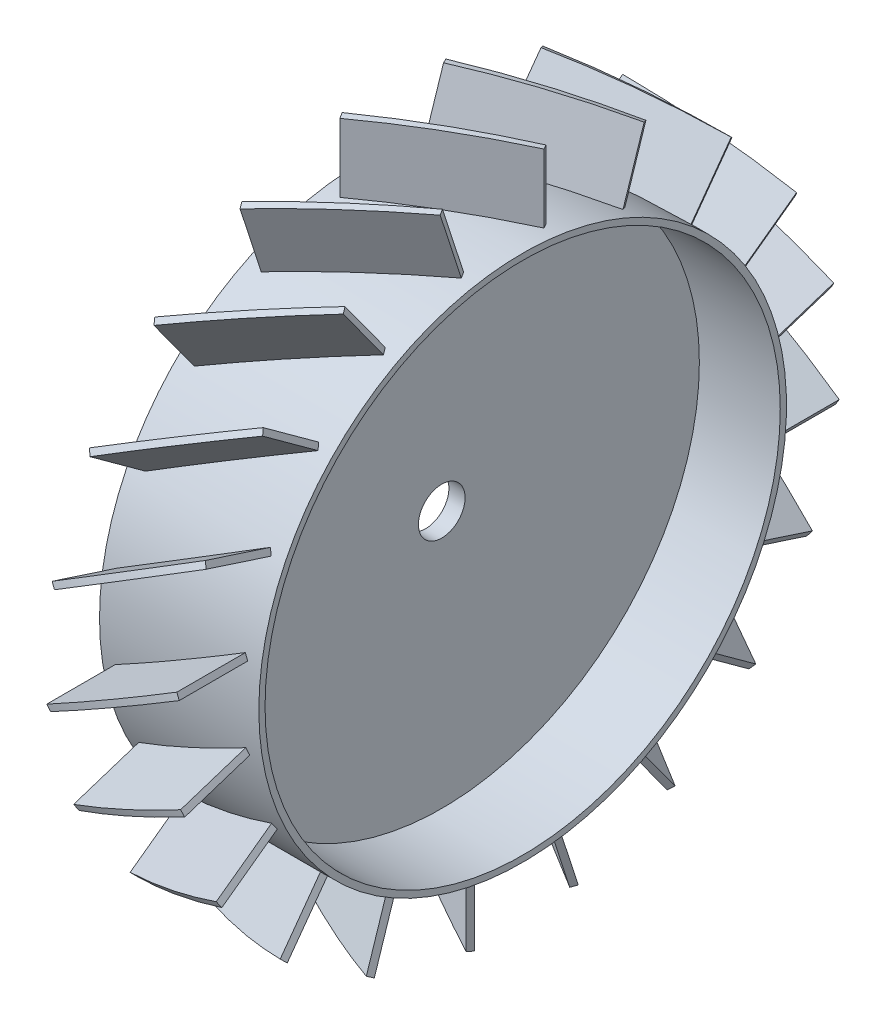
SolidWorks part; units mm, degrees
ref_plane "Front Plane" through (0, 0, 0) normal (0, 0, 1) x (1, 0, 0)
ref_plane "Top Plane" through (0, 0, 0) normal (0, 1, 0) x (1, 0, 0)
ref_plane "Right Plane" through (0, 0, 0) normal (1, 0, 0) x (0, 0, -1)
sketch "Sketch1" plane through (0, 0, 0) normal (0, 1, 0) x (1, 0, 0)
  line L0 (3.302, 0) -> (3.302, 52.578)
  line L1 (3.302, 52.578) -> (19.812, 52.578)
  line L2 (19.812, 52.578) -> (19.812, 53.848)
  line L3 (19.812, 53.848) -> (-12.7, 53.848)
  line L4 (-12.7, 53.848) -> (-12.7, 52.578)
  line L5 (-12.7, 52.578) -> (0, 52.578)
  line L6 (0, 52.578) -> (0, 0)
  line L7 (0, 0) -> (3.302, 0)
  dimension "D1" = 3.302
  dimension "D2" = 1.27
  dimension "D3" = 52.578
  dimension "D4" = 32.512
  dimension "D5" = 12.7
revolve "Revolve1" add sketch "Sketch1" angle 360 about L7
ref_plane "Plane1" through (0, 0, 83.82) normal (0, 0, 1) x (1, 0, 0)
sketch "Sketch2" plane through (0, 0, 83.82) normal (0, 0, 1) x (1, 0, 0)
  line L0 (-9.3247, -8.1699) -> (17.0717, 7.0701)
  line L1 (17.0717, 7.0701) -> (16.4367, 8.1699)
  line L3 (16.4367, 8.1699) -> (-9.9597, -7.0701)
  line L4 (-9.9597, -7.0701) -> (-9.3247, -8.1699)
  line L5 (-12.7, 0) -> (19.812, 0) construction
  line L6 (-12.7, 53.848) -> (-12.7, -53.848) construction
  line L7 (19.812, -53.848) -> (19.812, 53.848) construction
  line L8 (3.8735, -0.5499) -> (3.2385, 0.5499) construction
  point P4 (3.556, 0)
  point P13 (3.556, 0)
  dimension "D1" = 1.27
  dimension "D2" = 30
  dimension "D3" = 30.48
extrude "Boss-Extrude1" add sketch "Sketch2" along normal blind 13.97 from surface starting at face at (-12.7, 0, 53.848)
pattern_circular "CirPattern15" count 20 over 360 about axis through (19.812, 0, 0) along (-1, 0, 0) of "Boss-Extrude1"
sketch "Sketch7" plane through (0, 0, 0) normal (-1, 0, 0) x (0, 0, 1)
  circle A0 centre (0, 0) radius 4.7625
  dimension "D1" = 9.525
extrude "Cut-Extrude1" cut sketch "Sketch7" against normal through all
